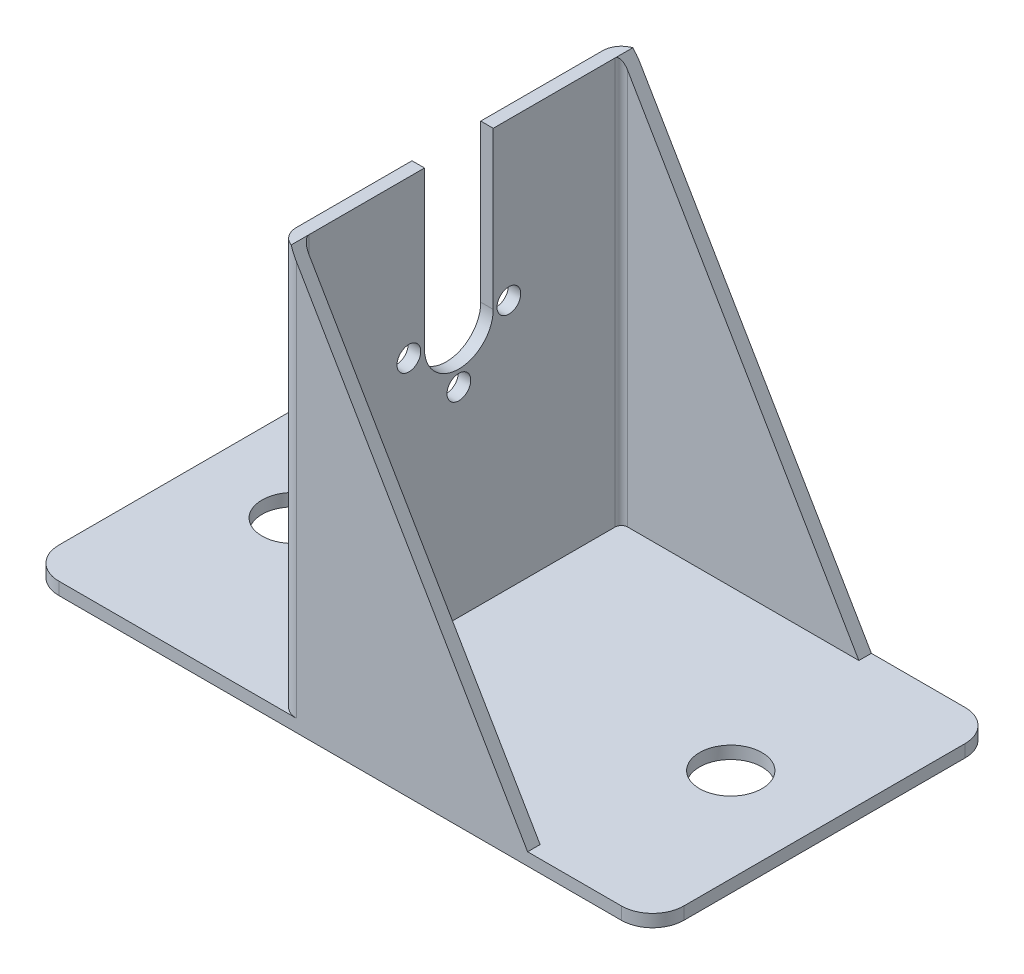
SolidWorks part; units mm, degrees
ref_plane "Alzado" through (0, 0, 0) normal (0, 0, 1) x (1, 0, 0)
ref_plane "Planta" through (0, 0, 0) normal (0, 1, 0) x (1, 0, 0)
ref_plane "Vista lateral" through (0, 0, 0) normal (1, 0, 0) x (0, 0, -1)
sketch "Croquis1" plane through (0, 0, 0) normal (0, 1, 0) x (1, 0, 0)
  line L1 (-50, -27.5) -> (50, -27.5)
  line L2 (-50, -27.5) -> (-50, 27.5)
  line L3 (-50, 27.5) -> (50, 27.5)
  line L4 (50, -27.5) -> (50, 27.5)
  line L5 (-50, -27.5) -> (50, 27.5) construction
  line L6 (-50, 27.5) -> (50, -27.5) construction
  point P0 (0, 0)
  dimension "D1" = 55
  dimension "D2" = 100
extrude "Saliente-Extruir1" add sketch "Croquis1" along normal blind 2
sketch "Croquis2" plane through (0, 2, 0) normal (0, 1, 0) x (1, 0, 0)
  line L0 (0, 27.5) -> (0, -27.5) construction
  line L1 (50, 27.5) -> (-50, 27.5) construction
  line L2 (-50, -27.5) -> (50, -27.5) construction
  line L3 (-35, 0) -> (35, 0) construction
  circle A0 centre (35, 0) radius 5
  circle A1 centre (-35, 0) radius 5
  point P9 (0, 0)
  dimension "D1" = 10
  dimension "D2" = 70
extrude "Cortar-Extruir1" cut sketch "Croquis2" against normal up to surface (2 mm away) up to face at (0, 0, 0)
sketch "Croquis3" plane through (0, 2, 0) normal (0, 1, 0) x (1, 0, 0)
  line L0 (30, 27.5) -> (-7, 27.5)
  line L1 (50, 27.5) -> (-50, 27.5) construction
  line L2 (-10, 24.5) -> (-10, -24.5)
  line L3 (-50, -27.5) -> (50, -27.5) construction
  line L4 (-7, -27.5) -> (30, -27.5)
  line L5 (30, 25.5) -> (-7, 25.5)
  line L6 (-8, 24.5) -> (-8, -24.5)
  line L7 (-7, -25.5) -> (30, -25.5)
  line L8 (30, 27.5) -> (30, 25.5)
  line L9 (30, -25.5) -> (30, -27.5)
  arc A0 (-10, -24.5) -> (-7, -27.5) centre (-7, -24.5) ccw
  arc A1 (-7, 27.5) -> (-10, 24.5) centre (-7, 24.5) ccw
  arc A2 (-7, 25.5) -> (-8, 24.5) centre (-7, 24.5) ccw
  arc A3 (-8, -24.5) -> (-7, -25.5) centre (-7, -24.5) ccw
  point P9 (0, 0)
  point P12 (-10, -27.5)
  point P15 (-10, 27.5)
  dimension "D3" = 3
  dimension "D1" = 40
  dimension "D2" = 10
  dimension "D4" = 2
extrude "Saliente-Extruir2" add sketch "Croquis3" along normal blind 65
sketch "Croquis4" plane through (0, 0, 27.5) normal (0, 0, 1) x (1, 0, 0)
  line L0 (-8, 67) -> (-8, 2) construction
  line L1 (-8, 67) -> (-8, 2) construction
  line L2 (-8, 67) -> (30, 2)
  line L3 (30, 2) -> (30, 67)
  line L4 (30, 67) -> (-8, 67)
extrude "Cortar-Extruir2" cut sketch "Croquis4" against normal up to surface (55 mm away) up to face at (5.75, 17.75, -27.5)
sketch "Croquis5" plane through (-10, 0, 0) normal (-1, 0, 0) x (0, 0, 1)
  circle A0 centre (0.5, 41.9) radius 12 construction
  circle A1 centre (0.5, 41.9) radius 12
  circle A2 centre (-15.75, 41.9) radius 2.25 construction
  circle A3 centre (-15.75, 41.9) radius 2.25 construction
  circle A4 centre (-10.8799, 30.3) radius 2.25 construction
  circle A5 centre (11.8799, 30.3) radius 2.25 construction
  circle A6 centre (16.75, 41.9) radius 2.25 construction
  circle A7 centre (11.8799, 53.5) radius 2.25 construction
  circle A8 centre (-15.75, 41.9) radius 2.25
  circle A9 centre (-15.75, 41.9) radius 2.25
  circle A10 centre (-10.8799, 30.3) radius 2.25
  circle A11 centre (11.8799, 30.3) radius 2.25
  circle A12 centre (16.75, 41.9) radius 2.25
  circle A13 centre (11.8799, 53.5) radius 2.25
  circle A14 centre (-10.8799, 53.5) radius 2.25 construction
  circle A15 centre (-10.8799, 53.5) radius 2.25
fillet "Redondeo1" radius 5 4 edges at (-50, 1, 27.5) (-50, 1, -27.5) (50, 1, -27.5) (50, 1, 27.5)
sketch "Croquis6" plane through (-8, 0, 0) normal (1, 0, 0) x (0, 0, -1)
  line L0 (-0.5, 41.9) -> (-0.5, 67) construction
  line L1 (-24.5, 67) -> (24.5, 67) construction
  line L2 (-6, 41.9) -> (-6, 67)
  line L3 (5, 41.9) -> (5, 67)
  line L4 (-6, 67) -> (5, 67)
  circle A0 centre (-0.5, 41.9) radius 4 construction
  circle A1 centre (-0.5, 41.9) radius 4 construction
  circle A2 centre (-0.5, 41.9) radius 5.5 construction
  arc A3 (-6, 41.9) -> (5, 41.9) centre (-0.5, 41.9) ccw
  circle A4 centre (-0.5, 41.9) radius 8 construction
  circle A5 centre (-8.5, 41.9) radius 1.9
  circle A6 centre (-0.5, 33.9) radius 1.9
  circle A7 centre (7.5, 41.9) radius 1.9
  dimension "D1" = 11
  dimension "D2" = 16
  dimension "D3" = 3.8
extrude "Cortar-Extruir3" cut sketch "Croquis6" against normal up to surface (2 mm away) up to face at (-10, 34.5, 0)
